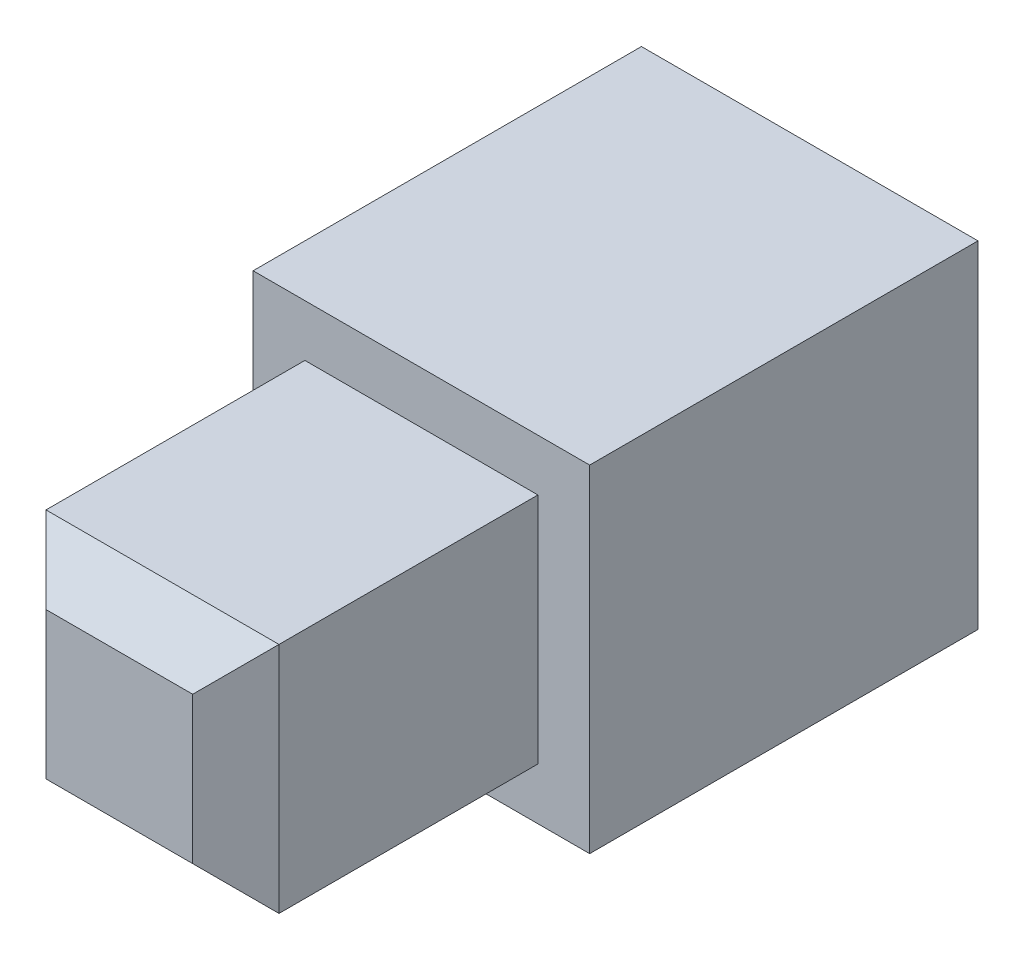
SolidWorks part; units mm, degrees
ref_plane "Front Plane" through (0, 0, 0) normal (0, 0, 1) x (1, 0, 0)
ref_plane "Top Plane" through (0, 0, 0) normal (0, 1, 0) x (1, 0, 0)
ref_plane "Right Plane" through (0, 0, 0) normal (1, 0, 0) x (0, 0, -1)
sketch "Sketch2" plane through (0, 0, 100.3354) normal (0, 0, 1) x (1, 0, 0)
  line L0 (-15.0508, 92.6158) -> (-15.0508, 87.4158) construction
  line L1 (-16.0508, 93.9158) -> (-8.2508, 93.9158)
  line L2 (-16.0508, 93.9158) -> (-16.0508, 86.1158)
  line L3 (-16.0508, 86.1158) -> (-8.2508, 86.1158)
  line L4 (-8.2508, 93.9158) -> (-8.2508, 86.1158)
  line L5 (-9.5508, 92.9158) -> (-14.7508, 92.9158) construction
  line L6 (-9.2508, 87.4158) -> (-9.2508, 92.6158) construction
  line L7 (-14.7508, 87.1158) -> (-9.5508, 87.1158) construction
  dimension "D1" = 1
  dimension "D2" = 1
  dimension "D3" = 1
  dimension "D4" = 1
extrude "Boss-Extrude1" add sketch "Sketch2" along normal blind 5
sketch "Sketch3" plane through (0, 0, 100.3354) normal (0, 0, -1) x (-1, 0, 0)
  line L0 (16.0508, 93.9158) -> (16.0508, 86.1158) construction
  line L1 (16.0508, 86.1158) -> (8.2508, 86.1158) construction
  line L2 (8.2508, 86.1158) -> (8.2508, 93.9158) construction
  line L3 (8.2508, 93.9158) -> (16.0508, 93.9158) construction
  line L4 (16.0508, 93.9158) -> (16.0508, 86.1158)
  line L5 (16.0508, 86.1158) -> (8.2508, 86.1158)
  line L6 (8.2508, 86.1158) -> (8.2508, 93.9158)
  line L7 (8.2508, 93.9158) -> (16.0508, 93.9158)
  line L8 (9.0508, 93.1158) -> (15.2508, 93.1158)
  line L9 (15.2508, 93.1158) -> (15.2508, 86.9158)
  line L10 (15.2508, 86.9158) -> (9.0508, 86.9158)
  line L11 (9.0508, 86.9158) -> (9.0508, 93.1158)
  dimension "D1" = 0.8
extrude "Boss-Extrude2" add sketch "Sketch3" along normal blind 4
sketch "Sketch4" plane through (0, 0, 105.3354) normal (0, 0, 1) x (1, 0, 0)
  line L0 (-9.1508, 93.0158) -> (-15.1508, 93.0158) construction
  line L1 (-14.8508, 92.7158) -> (-9.4508, 92.7158)
  line L2 (-14.8508, 92.7158) -> (-14.8508, 87.3158)
  line L3 (-14.8508, 87.3158) -> (-9.4508, 87.3158)
  line L4 (-9.4508, 92.7158) -> (-9.4508, 87.3158)
  line L5 (-15.1508, 93.0158) -> (-15.1508, 87.0158) construction
  line L6 (-15.1508, 87.0158) -> (-9.1508, 87.0158) construction
  line L7 (-9.1508, 87.0158) -> (-9.1508, 93.0158) construction
  dimension "D1" = 0.3
  dimension "D2" = 0.3
  dimension "D3" = 0.3
  dimension "D4" = 0.3
extrude "Boss-Extrude3" add sketch "Sketch4" along normal blind 7
chamfer "Chamfer1" distance 1 angle 45 4 edges at (-12.1508, 92.7158, 112.3354) (-9.4508, 90.0158, 112.3354) (-12.1508, 87.3158, 112.3354) (-14.8508, 90.0158, 112.3354)
